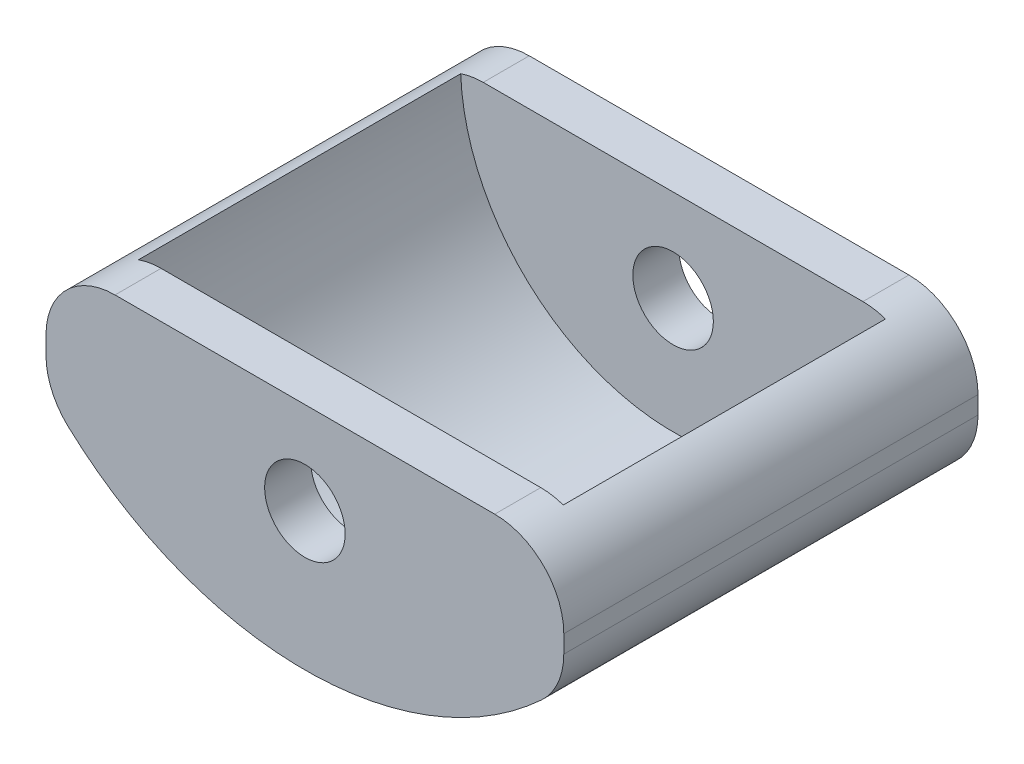
SolidWorks part; units mm, degrees
ref_plane "Front Plane" through (0, 0, 0) normal (0, 0, 1) x (1, 0, 0)
ref_plane "Top Plane" through (0, 0, 0) normal (0, 1, 0) x (1, 0, 0)
ref_plane "Right Plane" through (0, 0, 0) normal (1, 0, 0) x (0, 0, -1)
sketch "Sketch1" plane through (0, 0, 0) normal (0, 1, 0) x (1, 0, 0)
  line L1 (-11.25, 9) -> (11.25, 9)
  line L2 (-11.25, 9) -> (-11.25, -9)
  line L3 (-11.25, -9) -> (11.25, -9)
  line L4 (11.25, 9) -> (11.25, -9)
  dimension "D1" = 18
  dimension "D2" = 9
  dimension "D3" = 22.5
  dimension "D4" = 11.25
extrude "Boss-Extrude1" add sketch "Sketch1" along normal blind 10
sketch "Sketch2" plane through (0, 0, 9) normal (0, 0, 1) x (1, 0, 0)
  line L0 (-11.25, 10) -> (-11.25, 0) construction
  line L1 (11.25, 10) -> (11.25, 0) construction
  line L2 (-11.25, 5) -> (-11.25, 0)
  line L3 (-11.25, 0) -> (11.25, 0)
  line L4 (11.25, 0) -> (11.25, 5)
  line L5 (-11.25, 10) -> (11.25, 10) construction
  arc A0 (-11.25, 5) -> (11.25, 5) centre (0, 15.1866) ccw
  circle A1 centre (0, 6) radius 1.75
  point P19 (0, 0.01)
  dimension "D1" = 3.5
  dimension "D2" = 11.25
  dimension "D3" = 4
  dimension "D4" = 5.99
extrude "Cut-Extrude1" cut sketch "Sketch2" against normal through all and the other way through all
ref_plane "Plane1" through (0, 0, 7) normal (0, 0, 1) x (1, 0, 0)
sketch "Sketch3" plane through (0, 0, 7) normal (0, 0, 1) x (1, 0, 0)
  line L5 (-7.5, 10) -> (7.5, 10)
  line L6 (11.25, 10) -> (-11.25, 10) construction
  line L7 (-5.7661, 10.0479) -> (5.7661, 10.0479)
  arc A3 (-7.5, 10) -> (7.5, 10) centre (0, 10.2071) ccw construction
  arc A4 (-9.2339, 9.9521) -> (9.2339, 9.9521) centre (0, 10.2071) ccw
  arc A5 (-5.7661, 10.0479) -> (5.7661, 10.0479) centre (0, 10.2071) ccw
  arc A6 (-5.7661, 10.0479) -> (-9.2339, 9.9521) centre (-7.5, 10) ccw
  arc A7 (9.2339, 9.9521) -> (5.7661, 10.0479) centre (7.5, 10) ccw
  arc A8 (-5.7661, 10.0479) -> (5.7661, 10.0479) centre (0, 10.2071) ccw
  point P5 (0, 2.7043)
  point P16 (0, 10)
  dimension "D3" = 5.7683
  dimension "D1" = 15
  dimension "D2" = 3.75
  dimension "D4" = 7.2957
extrude "Cut-Extrude2" cut sketch "Sketch3" against normal blind 14 contours A5 A7 A4 A6
sketch "Sketch4" plane through (0, 10, 0) normal (0, 1, 0) x (1, 0, 0)
  line L1 (-5.7645, 7) -> (5.7645, 7)
  line L2 (-5.7645, 7) -> (-5.7645, -7)
  line L3 (-5.7645, -7) -> (5.7645, -7)
  line L4 (5.7645, 7) -> (5.7645, -7)
extrude "Cut-Extrude3" cut sketch "Sketch4" against normal up to surface (7.011 mm away) up to face at (0, 5.4609, 0)
fillet "Fillet1" radius 3 4 edges at (11.25, 5, 0) (-11.25, 5, 0) (11.25, 10, 0) (-11.25, 10, 0)
